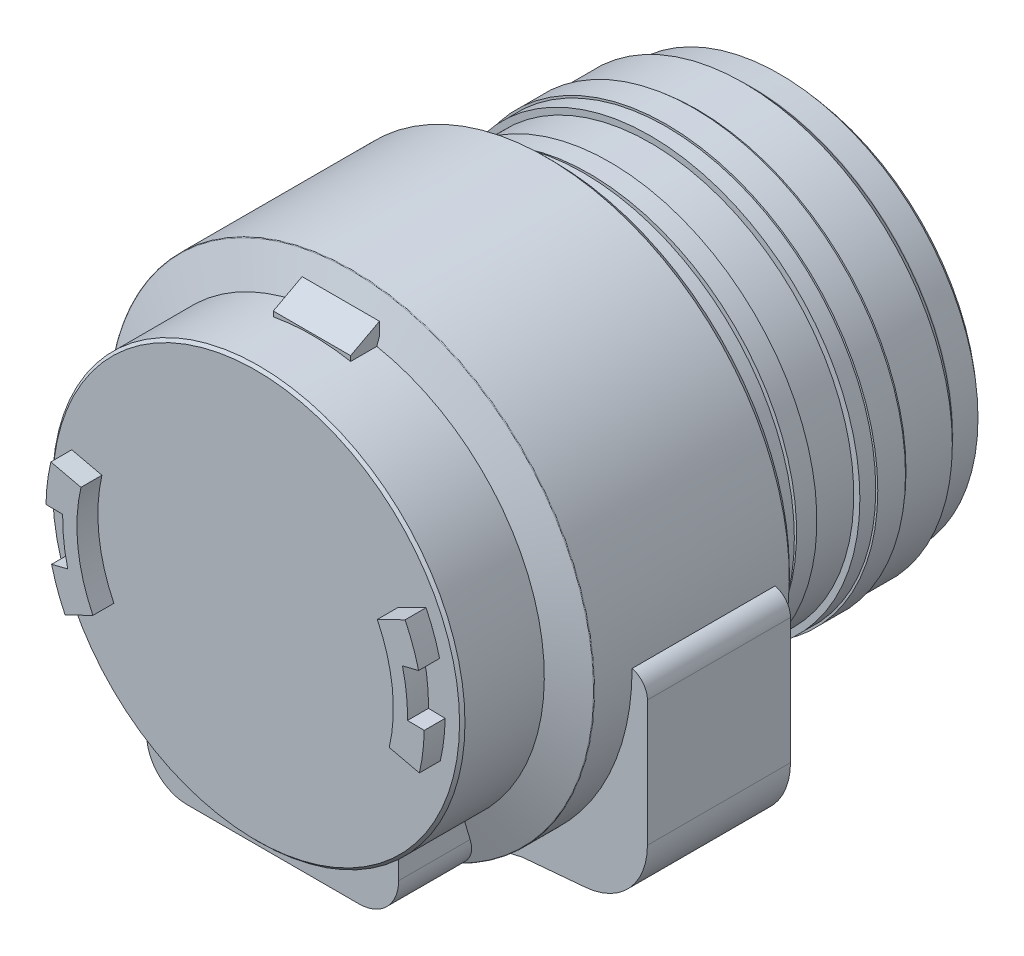
SolidWorks part; units mm, degrees
ref_plane "Front Plane" through (0, 0, 0) normal (0, 0, 1) x (1, 0, 0)
ref_plane "Top Plane" through (0, 0, 0) normal (0, 1, 0) x (1, 0, 0)
ref_plane "Right Plane" through (0, 0, 0) normal (1, 0, 0) x (0, 0, -1)
sketch "Sketch1" plane through (0, 0, 0) normal (0, 0, 1) x (1, 0, 0)
  circle A0 centre (0, 0) radius 35.9
extrude "Boss-Extrude1" add sketch "Sketch1" along normal blind 7.62 and the other way blind 24.25
sketch "Sketch2" plane through (0, 0, 7.62) normal (0, 0, 1) x (1, 0, 0)
  circle A0 centre (0, 0) radius 30.5
extrude "Boss-Extrude2" add sketch "Sketch2" along normal blind 12.1
sketch "Sketch3" plane through (0, 0, 7.62) normal (0, 0, 1) x (1, 0, 0)
  line L0 (0, 30.5) -> (16.9737, 30.5) construction
  line L1 (-18.625, -33.1) -> (18.625, -33.1)
  line L2 (-18.625, -33.1) -> (-18.625, 33.1)
  line L3 (-18.625, 33.1) -> (18.625, 33.1)
  line L4 (18.625, -33.1) -> (18.625, 33.1)
  line L5 (-18.625, -33.1) -> (18.625, 33.1) construction
  line L6 (-18.625, 33.1) -> (18.625, -33.1) construction
  circle A1 centre (0, 0) radius 30.5 construction
  circle A2 centre (0, 0) radius 30.5 construction
  point P0 (0, 0)
  circle M1 centre (0, 0) radius 35.9
  circle M2 centre (0, 0) radius 30.5
  dimension "D1" = 37.25
  dimension "D2" = 63.6
extrude "Boss-Extrude3" add sketch "Sketch3" along normal blind 9.64 and the other way blind 5 contours L4 L2 L1 M1 M2 | L1 L4 M1 | L2 L1 M1 region at (-17.0998, -32.3207, 7.62) region at (-16.1329, -31.6414, 7.62) region at (17.0998, -32.3207, 7.62)
chamfer "Chamfer1" distance 2 angle 70 1 edges at (0, 35.9, 7.62) first distance on face at (0, -23.9434, 5.12)
chamfer "Chamfer2" distance 0.4 angle 45 1 edges at (30.5, 0, 19.72)
fillet "Fillet1" radius 5.9 2 edges at (-18.625, -33.1, 9.94) (18.625, -33.1, 9.94)
sketch "Sketch9" plane through (0, 0, 0) normal (0, 0, 1) x (1, 0, 0)
  line L0 (-12.725, -33.1) -> (12.725, -33.1) construction
  line L1 (-10.0269, 33.1) -> (10.0269, 33.1)
  line L2 (-10.0269, 33.1) -> (-10.0269, -33.1)
  line L3 (-10.0269, -33.1) -> (10.0269, -33.1)
  line L4 (10.0269, 33.1) -> (10.0269, -33.1)
  line L5 (-10.0269, 33.1) -> (10.0269, -33.1) construction
  line L6 (-10.0269, -33.1) -> (10.0269, 33.1) construction
  line L7 (0, -33.1) -> (44.3345, -33.1)
  line L8 (44.3345, -33.1) -> (-49.2496, -33.1)
  line L9 (-34.8619, -33.1) -> (-34.8619, -56.3652)
  line L10 (-34.8619, -56.3652) -> (29.0553, -56.3652)
  line L11 (29.0553, -56.3652) -> (29.0553, -33.1)
  point P0 (0, 0)
extrude "Cut-Extrude4" cut sketch "Sketch9" against normal blind 100 and the other way blind 100 contours L10 L11 L7 L3 L8 L9 region at (-2.9033, -44.7326, 0)
ref_plane "Plane1" through (0, 0, 7.5854) normal (0, 0, 1) x (1, 0, 0)
sketch "Sketch10" plane through (0, 0, 7.5854) normal (0, 0, 1) x (1, 0, 0)
  line L0 (0, 30.5) -> (5.72, 30.5)
  line L1 (5.72, 30.5) -> (5.72, 33.1)
  line L2 (5.72, 33.1) -> (-5.72, 33.1)
  line L3 (-5.72, 33.1) -> (-5.72, 29.9588)
  line L4 (5.72, 30.5) -> (5.72, 29.9588)
  arc A0 (18.625, -24.1528) -> (-18.625, -24.1528) centre (0, 0) ccw construction
  circle A1 centre (0, 0) radius 30.5 construction
  arc A2 (-5.72, 29.9588) -> (5.72, 29.9588) centre (0, 0) cw
  dimension "D1" = 2.6
  dimension "D2" = 5.72
  dimension "D3" = 11.44
extrude "Boss-Extrude4" add sketch "Sketch10" along normal blind 3.87 and the other way blind 0.4 contours L3 A2 L0 L1 L2 | L0 A2 L4 region at (-0.1434, 31.7511, 7.5854) region at (4.2925, 30.3379, 7.5854)
chamfer "Chamfer3" distance 4.5 angle 28 1 edges at (0, 33.1, 11.4554) first distance on face at (0, 33.1, 9.3204)
fillet "Fillet2" radius 0.1 1 edges at (0, 35.9, 5.62)
sketch "Sketch12" plane through (0, 0, 0) normal (0, 0, 1) x (1, 0, 0)
  line L0 (-12.725, -33.1) -> (12.725, -33.1) construction
  line L1 (-38.1658, -33.6) -> (38.1658, -33.6)
  line L2 (-38.1658, -33.6) -> (-38.1658, 33.6)
  line L3 (-38.1658, 33.6) -> (38.1658, 33.6)
  line L4 (38.1658, -33.6) -> (38.1658, 33.6)
  line L5 (-38.1658, -33.6) -> (38.1658, 33.6) construction
  line L6 (-38.1658, 33.6) -> (38.1658, -33.6) construction
  line L7 (-35.8342, 0) -> (-35.8342, 33.6) construction
  line L8 (35.8342, 0) -> (38.1658, 0)
  line L9 (38.1658, 0) -> (38.1658, -4.1162)
  line L10 (0, -33.6) -> (13.8996, -33.6)
  line L11 (13.8996, -33.6) -> (19.6713, -32.2927)
  line L12 (19.6713, -32.2927) -> (38.1658, -30.6839)
  line L13 (13.8996, -33.1) -> (13.8996, -33.6) construction
  line L14 (19.6713, -32.2927) -> (-33.9813, -32.2927) construction
  line L15 (-16.6541, -32.2927) -> (-29, -30.6839)
  line L16 (-29, -30.6839) -> (-35.4558, -5.1941)
  line L17 (0, 0) -> (0, -57.2336) construction
  line L18 (-32.7798, -15.76) -> (-32.2955, -15.5271)
  line L19 (36.3342, 0) -> (35.8342, 0)
  line L20 (13.8996, -33.1) -> (13.8996, -33.6)
  line L21 (-13.828, -33.6) -> (-13.8996, -33.1)
  line L22 (-13.8996, -33.1) -> (13.8996, -33.1)
  arc A0 (16.2213, -31.9524) -> (-16.2213, -31.9524) centre (0, 0) ccw construction
  circle A1 centre (0, 0) radius 36.3342
  arc A2 (-32.2955, -15.5271) -> (35.8342, 0) centre (0, 0) ccw
  spline S0 degree 1 poles (35.8342, 0) (38.1658, 0) knots 0 0 1 1
  spline S2 degree 1 poles (13.8996, -33.6) (19.6713, -32.2927) knots 0 0 1 1
  point P0 (0, 0)
  dimension "D3" = 0.5
  dimension "D1" = 0.5
  dimension "D2" = 74
  dimension "D4" = 29
extrude "Boss-Extrude5" add sketch "Sketch12" against normal blind 21.16 contours A2 L18 A1 L1 | A1 L18 L16 L15 | A2 L10 A1 L8 | A1 L10 L11 L12 L4 L8 | A2 L10 A1 L20 L22 | L22 A2 L1 | A2 L22 L21 L1 region at (-13.3953, -33.4159, 0) region at (-15.1449, -32.7385, 0) region at (0, -33.346, 0) region at (-26.5887, -27.0321, 0) region at (13.4157, -33.4162, 0) region at (32.3234, -22.1056, 0) region at (14.3044, -33.3352, 0)
fillet "Fillet3" radius 10 1 edges at (38.1658, -30.6839, -10.58)
fillet "Fillet4" radius 6 1 edges at (-29, -30.6839, -10.58)
fillet "Fillet5" radius 3 1 edges at (38.1658, 0, -10.58)
chamfer "Chamfer4" distance 0.4 angle 31 1 edges at (-32.7798, -15.76, -10.58) first distance on face at (-31.3901, -21.2469, -10.58)
sketch "Sketch13" plane through (0, 0, -24.25) normal (0, 0, -1) x (-1, 0, 0)
  circle A0 centre (0, 0) radius 31.21
extrude "Boss-Extrude6" add sketch "Sketch13" along normal blind 4.44
sketch "Sketch14" plane through (0, 0, -28.69) normal (0, 0, -1) x (-1, 0, 0)
  circle A0 centre (0, 0) radius 29
extrude "Boss-Extrude7" add sketch "Sketch14" along normal blind 0.9
sketch "Sketch15" plane through (0, 0, -29.59) normal (0, 0, -1) x (-1, 0, 0)
  circle A0 centre (0, 0) radius 30.64
extrude "Boss-Extrude8" add sketch "Sketch15" along normal blind 3
sketch "Sketch16" plane through (0, 0, -32.59) normal (0, 0, -1) x (-1, 0, 0)
  circle A0 centre (0, 0) radius 30.1
extrude "Boss-Extrude9" add sketch "Sketch16" along normal blind 6
sketch "Sketch17" plane through (0, 0, -38.59) normal (0, 0, -1) x (-1, 0, 0)
  circle A0 centre (0, 0) radius 31
extrude "Boss-Extrude10" add sketch "Sketch17" along normal blind 2.35
sketch "Sketch18" plane through (0, 0, -40.94) normal (0, 0, -1) x (-1, 0, 0)
  circle A0 centre (0, 0) radius 31.3
extrude "Boss-Extrude11" add sketch "Sketch18" along normal blind 4.1
sketch "Sketch19" plane through (0, 0, -45.04) normal (0, 0, -1) x (-1, 0, 0)
  circle A0 centre (0, 0) radius 30.4221
extrude "Boss-Extrude12" add sketch "Sketch19" along normal blind 0.5
sketch "Sketch20" plane through (0, 0, -45.54) normal (0, 0, -1) x (-1, 0, 0)
  circle A0 centre (0, 0) radius 30.875
extrude "Boss-Extrude13" add sketch "Sketch20" along normal blind 8.05
sketch "Sketch21" plane through (0, 0, -53.59) normal (0, 0, -1) x (-1, 0, 0)
  circle A0 centre (0, 0) radius 29.65
extrude "Boss-Extrude14" add sketch "Sketch21" along normal blind 5.1
sketch "Sketch22" plane through (0, 0, -58.69) normal (0, 0, -1) x (-1, 0, 0)
  circle A0 centre (0, 0) radius 24.065
extrude "Cut-Extrude5" cut sketch "Sketch22" against normal blind 3.6
sketch "Sketch23" plane through (0, 0, -55.09) normal (0, 0, -1) x (-1, 0, 0)
  line L1 (-12.5791, -9.725) -> (12.5791, -9.725)
  line L2 (-12.5791, -9.725) -> (-12.5791, 9.725)
  line L3 (-12.5791, 9.725) -> (12.5791, 9.725)
  line L4 (12.5791, -9.725) -> (12.5791, 9.725)
  line L5 (-12.5791, -9.725) -> (12.5791, 9.725) construction
  line L6 (-12.5791, 9.725) -> (12.5791, -9.725) construction
  circle A0 centre (0, 0) radius 15.9
  dimension "D1" = 19.45
  dimension "D2" = 31.8
extrude "Cut-Extrude6" cut sketch "Sketch23" against normal blind 5 contours L2 A0 | L1 L4 L3 L2 | L4 A0 region at (0, 0, -55.09) region at (13.9201, 0, -55.09) region at (-13.9201, 0, -55.09)
chamfer "Chamfer5" distance 5 angle 4 1 edges at (-29.65, 0, -58.69) first distance on face at (-29.65, 0, -58.69)
chamfer "Chamfer6" distance 1 angle 45 1 edges at (-29.3004, 0, -58.69) first distance on face at (-29.65, 0, -53.69)
chamfer "Chamfer7" distance 1.2 angle 45 1 edges at (-30.875, 0, -53.59)
chamfer "Chamfer8" distance 1 angle 45 1 edges at (0, 35.9, -24.25)
sketch "Sketch25" plane through (-34.5548, -8.7516, 0) normal (-0.9694, -0.2455, 0) x (0, 0, 1)
  line L0 (0, -13.0898) -> (-21.16, -13.0898) construction
  line L1 (0, -18.55) -> (0, -7.6296) construction
  line L2 (-21.16, -18.55) -> (-21.16, -7.6296) construction
  line L4 (-13.5, -18.5898) -> (0, -18.5898)
  line L5 (-13.5, -18.5898) -> (-13.5, -7.5898)
  line L6 (-13.5, -7.5898) -> (0, -7.5898)
  line L7 (0, -18.5898) -> (0, -7.5898)
  line L8 (-13.5, -18.5898) -> (0, -7.5898) construction
  line L9 (-13.5, -7.5898) -> (0, -18.5898) construction
  point P6 (-6.75, -13.0898)
  dimension "D1" = 13.5
  dimension "D2" = 11
extrude "Cut-Extrude12" cut sketch "Sketch25" against normal blind 0.5
ref_plane "Plane2" through (-34.6767, 9.2916, 0) normal (-0.9659, 0.2588, 0) x (0, 0, -1)
sketch "Sketch26" plane through (-34.6767, 9.2916, 0) normal (-0.9659, 0.2588, 0) x (0, 0, -1)
  line L0 (23.25, -1.4304) -> (13.6194, -1.4304) construction
  line L1 (23.25, -35.9) -> (23.25, 35.5696) construction
  line L2 (21.16, 35.5696) -> (23.25, 35.5696) construction
  circle A0 centre (13.6194, -1.4304) radius 4.81
  point P5 (22.205, 35.5696)
  dimension "D1" = 37
extrude "Boss-Extrude15" add sketch "Sketch26" against normal up to surface and the other way blind 0.5 up to face at (0.6936, -21.4455, -3.954)
sketch "Sketch27" plane through (0, 0, 19.72) normal (0, 0, 1) x (1, 0, 0)
  line L0 (-22.8003, 5.2639) -> (-27.258, 6.293)
  line L1 (-27.9707, 0.4882) -> (-25.5061, 0.4452)
  line L2 (-24.7522, -6.1714) -> (-27.144, -6.7678)
  line L3 (-21.0318, -10.2579) -> (-22.9282, -11.1828)
  line L4 (-12.725, -33.1) -> (12.725, -33.1) construction
  line L5 (-22.9282, -11.1828) -> (-25.1438, -12.2634)
  line L6 (-25.1438, -12.2634) -> (-22.8003, 5.2639) construction
  line L7 (-22.8003, 5.2639) -> (-27.258, 6.293) construction
  line L8 (-27.258, 6.293) -> (-21.0318, -10.2579) construction
  line L9 (-23.8677, -2.7194) -> (23.8677, 2.7194) construction
  line L10 (0, 0) -> (-0.8438, 7.4063) construction
  line L11 (-21.0318, -10.2579) -> (0, 0)
  line L12 (0, 0) -> (-4.5749, 9.38)
  line L13 (25.1438, 12.2634) -> (22.8003, -5.2639) construction
  line L14 (21.0318, 10.2579) -> (25.1438, 12.2634) construction
  line L15 (27.258, -6.293) -> (21.0318, 10.2579) construction
  line L16 (22.8003, -5.2639) -> (0, 0)
  line L17 (24.8562, -5.7385) -> (27.258, -6.293)
  line L18 (22.8003, -5.2639) -> (24.8562, -5.7385)
  line L19 (25.5061, -0.4452) -> (27.9707, -0.4882)
  line L20 (27.144, 6.7678) -> (24.7522, 6.1714)
  line L21 (21.0318, 10.2579) -> (25.1438, 12.2634)
  circle A0 centre (0, 0) radius 23.4
  circle A1 centre (0, 0) radius 27.975
  circle A2 centre (0, 0) radius 25.51
  dimension "D1" = 15
  dimension "D2" = 12
  dimension "D3" = 12
  dimension "D4" = 14
extrude "Boss-Extrude16" add sketch "Sketch27" along normal blind 3.1 contours A2 L2 A1 L5 | L0 A2 L3 A0 | A2 L0 A1 L1 | A2 L20 A1 L21 | A2 L21 A0 L18 | A2 L17 A1 L19 region at (-23.8462, -2.7169, 19.72) region at (-26.5134, 3.2554, 19.72) region at (23.8462, 2.7169, 19.72) region at (25.1016, 9.1362, 19.72) region at (-25.1016, -9.1362, 19.72) region at (26.5134, -3.2554, 19.72)
sketch "Sketch28" plane through (0, -33.6, 0) normal (0, -1, 0) x (1, 0, 0)
  line L0 (0, 0) -> (0, -14.9509) construction
  line L1 (13.8996, 0) -> (-13.8996, 0) construction
  circle A0 centre (0, -8) radius 2.5
  dimension "D2" = 5
  dimension "D1" = 8
hole_wizard "1/4-20 Tapped Hole1" positions "Sketch30" profile "Sketch29" tap size "1/4-20" standard "ANSI Inch"
sketch "Sketch30" plane through (0, -33.6, 0) normal (0, -1, 0) x (-1, 0, 0)
  point P0 (0, 8)
sketch "Sketch29" plane through (0, -33.6, -8) normal (1, 0, 0) x (0, 0, -1)
  line L0 (0, 0) -> (0, 9.5338)
  line L1 (0, 9.5338) -> (2.5527, 8)
  line L2 (2.5527, 8) -> (2.5527, 0)
  line L5 (2.5527, 0) -> (0, 0)
  line L10 (0, 9.5338) -> (-2.5527, 8) construction
  line L11 (0, -6.35) -> (0, 107.95) construction
  dimension "Tap Drill Dia." = 5.1054
  dimension "Tap Drill Depth" = 8
  dimension "Drill Angle" = 118
cosmetic thread "Hole Thread1" parameters "D1"=8, "D2"=6.35
equation "\"0.2.00mm\"=1"
